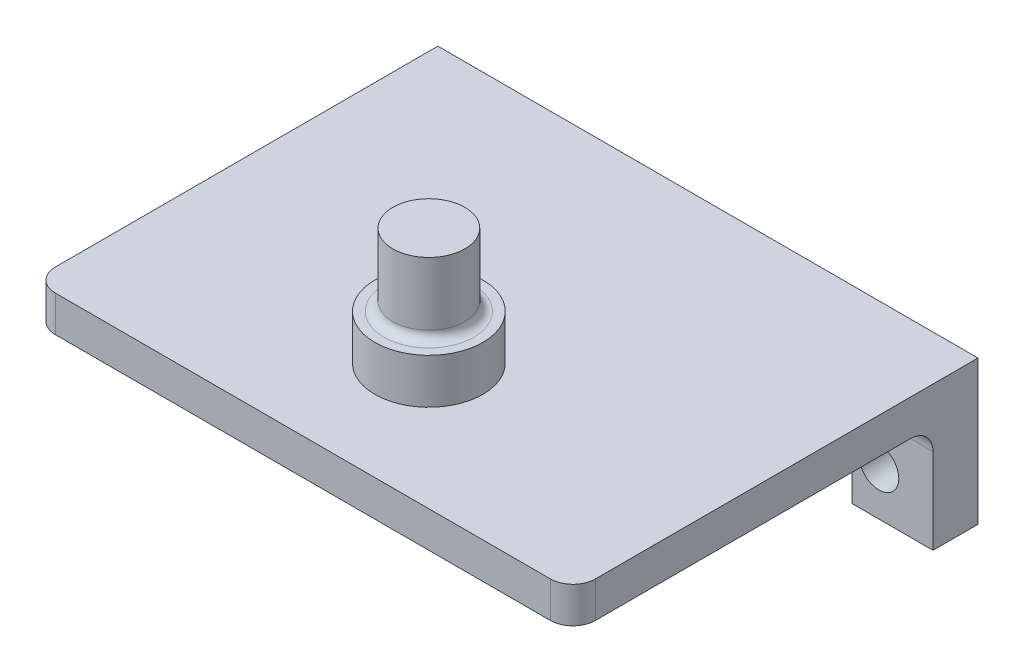
SolidWorks part; units mm, degrees
ref_plane "Front Plane" through (0, 0, 0) normal (0, 0, 1) x (1, 0, 0)
ref_plane "Top Plane" through (0, 0, 0) normal (0, 1, 0) x (1, 0, 0)
ref_plane "Right Plane" through (0, 0, 0) normal (1, 0, 0) x (0, 0, -1)
sketch "Sketch1" plane through (0, 0, 0) normal (0, 0, 1) x (1, 0, 0)
  line L0 (-82.0256, 30) -> (-82.0256, -25.5559) construction
  line L2 (-112.0256, 7.6852) -> (-112.0256, 27.1852)
  line L4 (-103.0256, 7.6852) -> (-103.0256, 27.1852)
  line L9 (-112.0256, 27.1852) -> (-112.0256, 31.6852)
  line L10 (-112.0256, 7.6852) -> (-52.0256, 7.6852)
  line L11 (-112.0256, 7.6852) -> (-112.0256, 3.6852)
  line L12 (-112.0256, 3.6852) -> (-52.0256, 3.6852)
  line L13 (-52.0256, 7.6852) -> (-52.0256, 3.6852)
  line L14 (-112.0256, 31.6852) -> (-103.0256, 31.6852)
  line L15 (-103.0256, 31.6852) -> (-103.0256, 27.1852)
  line L16 (-52.0256, 27.1852) -> (-52.0256, 31.6852)
  line L17 (-112.0256, 31.6852) -> (-52.0256, 31.6852)
  line L18 (-112.0256, 31.6852) -> (-112.0256, 35.6852)
  line L19 (-112.0256, 35.6852) -> (-52.0256, 35.6852)
  line L20 (-52.0256, 31.6852) -> (-52.0256, 35.6852)
  line L21 (-61.0256, 31.6852) -> (-61.0256, 27.1852)
  line L22 (-61.0256, 7.6852) -> (-61.0256, 27.1852)
  line L23 (-52.0256, 7.6852) -> (-52.0256, 27.1852)
  circle A0 centre (-106.0256, 24.6852) radius 2.2
  circle A1 centre (-106.0256, 14.6852) radius 2.2
  circle A2 centre (-58.0256, 14.6852) radius 2.2
  circle A3 centre (-58.0256, 24.6852) radius 2.2
  point P29 (-103.0256, 29.6852)
  point P32 (-112.0256, 29.6852)
  dimension "D3" = 4.4
  dimension "D4" = 4.4
  dimension "D12" = 3
  dimension "D1" = 22
  dimension "D2" = 4
  dimension "D5" = 10
  dimension "D6" = 7
  dimension "D7" = 60
  dimension "D8" = 42
  dimension "D9" = 4
  dimension "D10" = 55.5559
  dimension "D11" = 3
  dimension "D13" = 7
extrude "Boss-Extrude1" add sketch "Sketch1" along normal blind 45 contours L10 L0 L12 L13 | L0 L10 L11 L12 region at (-67.0256, 5.6852, 0) region at (-97.0256, 5.6852, 0)
extrude "Boss-Extrude2" add sketch "Sketch1<3>" along normal blind 5 contours L2 L10 L4 A1 A0 | L10 L23 L16 L17 L21 L22 A2 A3 region at (-107.7714, 19.6852, 0) region at (-56.2799, 19.6852, 0)
sketch "Sketch1<3>" plane through (0, 0, 0) normal (0, 0, 1) x (1, 0, 0) same geometry as "Sketch1"
sketch "Sketch2" plane through (0, 7.6852, 0) normal (0, 1, 0) x (1, 0, 0)
  line L0 (-82.0256, -6.4694) -> (-82.0256, -26.5346) construction
  line L1 (-96.5112, -31) -> (-67.862, -31) construction
  line L2 (-52.0256, -45) -> (-52.0256, -5) construction
  line L3 (-112.0256, -45) -> (-52.0256, -45) construction
  circle A0 centre (-82.0256, -31) radius 3
  circle A1 centre (-77.0256, -26) radius 1.6
  circle A2 centre (-87.0256, -26) radius 1.6
  circle A3 centre (-77.0256, -36) radius 1.6
  circle A4 centre (-87.0256, -36) radius 1.6
  dimension "D1" = 6
  dimension "D2" = 3.2
  dimension "D3" = 3.2
  dimension "D4" = 5
  dimension "D5" = 5
  dimension "D6" = 10
  dimension "D7" = 5
  dimension "D8" = 30
  dimension "D9" = 28.6493
  dimension "D10" = 14
extrude "Cut-Extrude1" cut sketch "Sketch2" against normal through all
extrude "Boss-Extrude3" add sketch "Sketch1<4>" along normal blind 45 contours L17 L20 L19 L18 L14 region at (-82.0256, 33.6852, 0)
sketch "Sketch1<4>" plane through (0, 0, 0) normal (0, 0, 1) x (1, 0, 0) same geometry as "Sketch1"
fillet "Fillet1" radius 2.5 4 edges at (-52.0256, 5.6852, 45) (-112.0256, 5.6852, 45) (-52.0256, 33.6852, 45) (-112.0256, 33.6852, 45)
fillet "Fillet3" radius 2.5 4 edges at (-107.5256, 7.6852, 5) (-56.5256, 7.6852, 5) (-56.5256, 31.6852, 5) (-107.5256, 31.6852, 5)
sketch "Sketch3" plane through (0, 35.6852, 0) normal (0, 1, 0) x (1, 0, 0)
  line L0 (-52.0256, -42.5) -> (-52.0256, 0) construction
  line L3 (-109.5256, -45) -> (-54.5256, -45) construction
  circle A0 centre (-82.0256, -31) radius 4
  dimension "D3" = 8
  dimension "D1" = 30
  dimension "D2" = 14
extrude "Boss-Extrude4" add sketch "Sketch3" along normal blind 13
sketch "Sketch4" plane through (0, 35.6852, 0) normal (0, 1, 0) x (1, 0, 0)
  circle A0 centre (-82.0256, -31) radius 6
  circle A1 centre (-82.0256, -31) radius 4 construction
  dimension "D1" = 2
extrude "Boss-Extrude5" add sketch "Sketch4" along normal blind 5
fillet "Fillet4" radius 1 1 edges at (-82.0256, 40.6852, 35)
sketch "Sketch6" plane through (-52.0256, 0, 0) normal (1, 0, 0) x (0, 0, -1)
  line L0 (0, 35.6852) -> (0, 3.6852) construction
  line L1 (0, 19.6852) -> (-45, 19.6852)
  line L2 (0, 19.6852) -> (0, 3.6852)
  line L3 (0, 3.6852) -> (-45, 3.6852)
  line L4 (-45, 19.6852) -> (-45, 3.6852)
extrude "Cut-Extrude2" cut sketch "Sketch6" against normal through all
